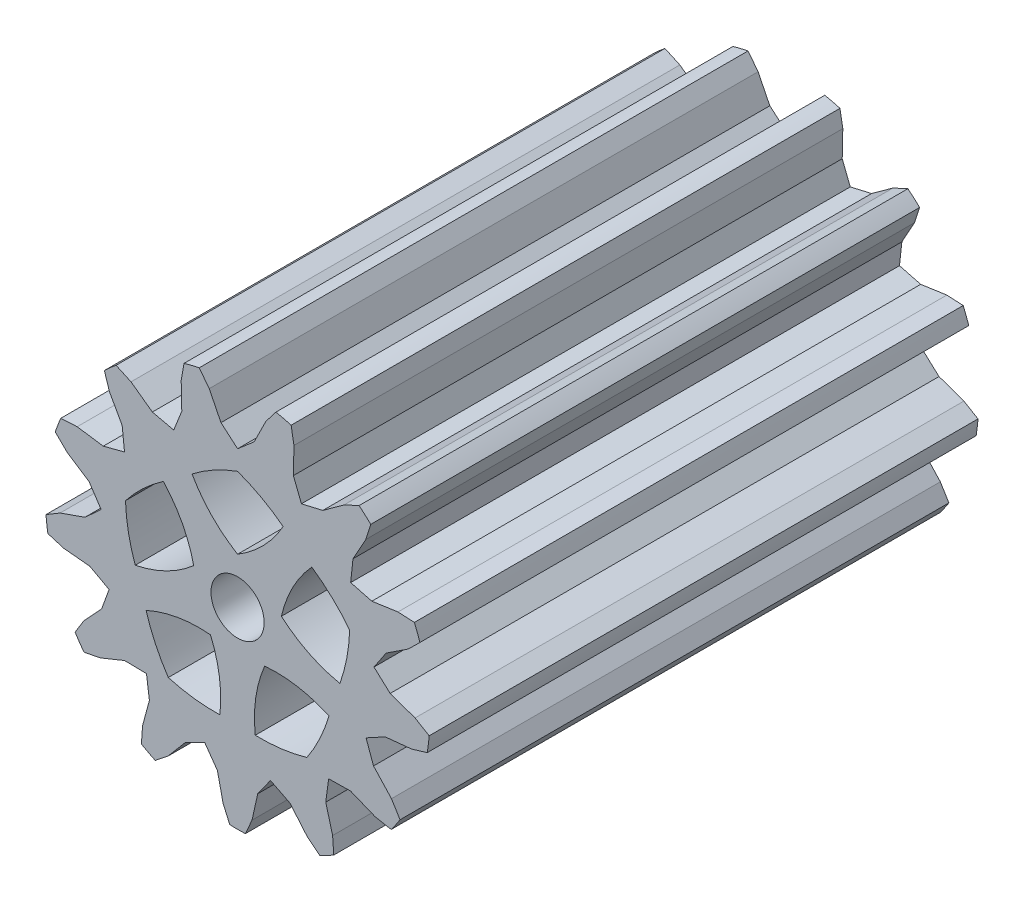
SolidWorks part; units mm, degrees
ref_plane "Front Plane" through (0, 0, 0) normal (0, 0, 1) x (1, 0, 0)
ref_plane "Top Plane" through (0, 0, 0) normal (0, 1, 0) x (1, 0, 0)
ref_plane "Right Plane" through (0, 0, 0) normal (1, 0, 0) x (0, 0, -1)
sketch "Sketch1" plane through (0, 0, 0) normal (0, 0, 1) x (1, 0, 0)
  line L1 (1.2374, -1.2374) -> (-1.2374, -1.2374) construction
  line L2 (1.2374, -1.2374) -> (1.2374, 1.2374) construction
  line L3 (1.2374, 1.2374) -> (-1.2374, 1.2374) construction
  line L4 (-1.2374, -1.2374) -> (-1.2374, 1.2374) construction
  line L5 (1.2374, -1.2374) -> (-1.2374, 1.2374) construction
  line L6 (1.2374, 1.2374) -> (-1.2374, -1.2374) construction
  circle A0 centre (0, 0) radius 11.5556
  circle A1 centre (0, 0) radius 1.75 construction
  dimension "D1" = 23.1111
  dimension "D2" = 3.5
extrude "Boss-Extrude1" add sketch "Sketch1" along normal blind 33
sketch "Sketch2" plane through (0, 0, 0) normal (0, 0, 1) x (1, 0, 0)
  line L0 (0, 0) -> (0, 10.088) construction
  line L1 (0, 8.2614) -> (-0.9985, 9.1208)
  line L8 (-1.7043, 12.1062) -> (0, 12.8204)
  line L11 (-0.9985, 9.1208) -> (-1.7043, 10.5419)
  line L12 (-1.7043, 10.5419) -> (-2.3066, 11.323)
  line L13 (-2.3066, 11.323) -> (-1.7043, 12.1062)
  line L14 (2.3066, 11.323) -> (1.7043, 12.1062)
  line L15 (1.7043, 10.5419) -> (2.3066, 11.323)
  line L16 (0.9985, 9.1208) -> (1.7043, 10.5419)
  line L17 (1.7043, 12.1062) -> (0, 12.8204)
  line L18 (0, 8.2614) -> (0.9985, 9.1208)
  circle A14 centre (0, 0) radius 11.5556 construction
  point P16 (0, 11.5556)
  dimension "D5" = 0.6023
  dimension "D6" = 0.7811
  dimension "D1" = 0.9985
  dimension "D2" = 0.8594
  dimension "D3" = 0.7058
  dimension "D4" = 1.4211
  dimension "D7" = 0.7832
  dimension "D8" = 0.6023
  dimension "D9" = 0.7142
  dimension "D10" = 1.7043
extrude "Cut-Extrude1" cut sketch "Sketch2" along normal through all
sketch "Sketch3" plane through (0, 0, 0) normal (0, 0, 1) x (1, 0, 0)
  circle A0 centre (0, 0) radius 7.5
  dimension "D1" = 15
sketch "Sketch4" plane through (0, 0, 33) normal (0, 0, 1) x (1, 0, 0)
  circle A0 centre (0, 0) radius 1.6
  dimension "D1" = 3.2
extrude "Cut-Extrude2" cut sketch "Sketch4" against normal through all both and the other way through all
pattern_circular "CirPattern1" count 13 over 360 about axis through (0, 0, 33) along (0, 0, -1) of "Cut-Extrude1" reverse direction yes
sketch "Sketch5" plane through (0, 0, 0) normal (0, 0, 1) x (1, 0, 0)
  line L0 (0, 0) -> (0, 16.5734) construction
  arc A0 (0, 2.7703) -> (-2.7395, 5.5802) centre (3.9333, 9.3453) cw
  arc A1 (-2.7395, 5.5802) -> (0, 7.0858) centre (3.4783, -2.4876) cw
  arc A2 (2.7395, 5.5802) -> (0, 7.0858) centre (-3.4783, -2.4876) ccw
  arc A3 (0, 2.7703) -> (2.7395, 5.5802) centre (-3.9333, 9.3453) ccw
  point P7 (0, 5.401)
  point P12 (-2.1224, 4.7242)
  point P13 (0, 6.9338)
  point P14 (-2.7395, 5.5802)
  point P15 (0, 7.0858)
extrude "Cut-Extrude4" cut sketch "Sketch5" along normal through all both and the other way through all
pattern_circular "CirPattern2" count 5 over 360 about axis through (0, 0, 0) along (0, 0, 1) of "Cut-Extrude4"
equation "\"circle\"=23.1111"
equation "\"D1@Sketch1\"=\"circle\""
equation "\"separator_width\"=45"
equation "\"big-gear-thiccness\"=2"
equation "\"D1@Boss-Extrude1\"=\"separator_width\" - \"big-gear-thiccness\"-10"
